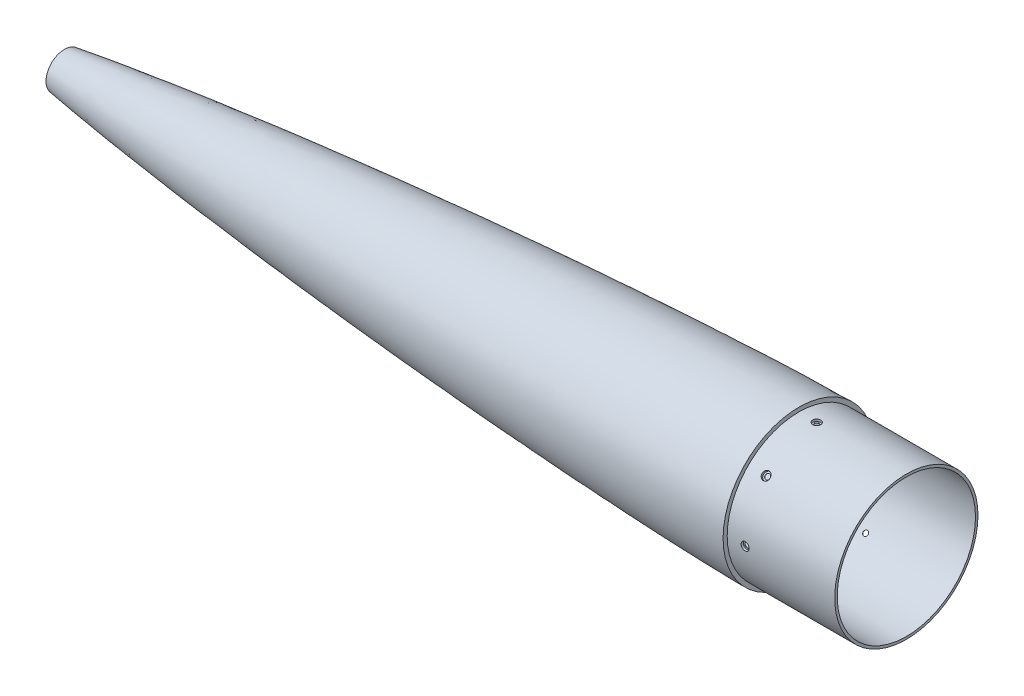
SolidWorks part; units mm, degrees
material "E-Glass Fiber"
ref_plane "Front Plane" through (0, 0, 0) normal (0, 0, 1) x (1, 0, 0)
ref_plane "Top Plane" through (0, 0, 0) normal (0, 1, 0) x (1, 0, 0)
ref_plane "Right Plane" through (0, 0, 0) normal (1, 0, 0) x (0, 0, -1)
sketch "Sketch2" plane through (0, 0, 0) normal (0, 0, 1) x (1, 0, 0)
  line L0 (0, 0) -> (584.2, 0)
  line L1 (584.2, 53.721) -> (584.2, 0)
  spline S0 degree 4 poles (0, 0) (0.0022, 0.0056) (0.0076, 0.0162) (0.0222, 0.0352) (0.0559, 0.0693) (0.1064, 0.1113) (0.1743, 0.1601) (0.2708, 0.2224) (0.3867, 0.2901) (0.5227, 0.3633) (0.6788, 0.4414) (0.9052, 0.5483) (1.2575, 0.7027) (1.8541, 0.9418) (2.9279, 1.3286) (4.8572, 1.9447) (8.3876, 2.9315) (14.9994, 4.5314) (26.6552, 6.951) (46.2509, 10.4452) (73.0277, 14.552) (105.3866, 18.9288) (141.1369, 23.265) (176.9301, 27.2281) (212.7562, 30.881) (248.6088, 34.2635) (284.4837, 37.3993) (320.3781, 40.3033) (356.29, 42.9823) (392.2179, 45.437) (428.1608, 47.6612) (464.1181, 49.6413) (495.5929, 51.1375) (522.5799, 52.2225) (544.3402, 52.9414) (558.9873, 53.3346) (571.0188, 53.5813) (578.5507, 53.684) (582.3169, 53.7167) (584.2, 53.721) knots 0 0 0 0 0 0.000041 0.000081 0.000163 0.000325 0.000488 0.00065 0.000944 0.001239 0.001539 0.001838 0.002649 0.003857 0.005913 0.009607 0.016434 0.028809 0.052217 0.090639 0.151931 0.213222 0.274513 0.335805 0.397096 0.458387 0.519679 0.58097 0.642262 0.703553 0.764844 0.826136 0.887427 0.918073 0.948719 0.974359 0.98718 1 1 1 1 1 construction
  spline S1 degree 4 poles (0, 0) (0.0022, 0.0056) (0.0076, 0.0162) (0.0222, 0.0352) (0.0559, 0.0693) (0.1064, 0.1113) (0.1743, 0.1601) (0.2708, 0.2224) (0.3867, 0.2901) (0.5227, 0.3633) (0.6788, 0.4414) (0.9052, 0.5483) (1.2575, 0.7027) (1.8541, 0.9418) (2.9279, 1.3286) (4.8572, 1.9447) (8.3876, 2.9315) (14.9994, 4.5314) (26.6552, 6.951) (46.2509, 10.4452) (73.0277, 14.552) (105.3866, 18.9288) (141.1369, 23.265) (176.9301, 27.2281) (212.7562, 30.881) (248.6088, 34.2635) (284.4837, 37.3993) (320.3781, 40.3033) (356.29, 42.9823) (392.2179, 45.437) (428.1608, 47.6612) (464.1181, 49.6413) (495.5929, 51.1375) (522.5799, 52.2225) (544.3402, 52.9414) (558.9873, 53.3346) (571.0188, 53.5813) (578.5507, 53.684) (582.3169, 53.7167) (584.2, 53.721) knots 0 0 0 0 0 0.000041 0.000081 0.000163 0.000325 0.000488 0.00065 0.000944 0.001239 0.001539 0.001838 0.002649 0.003857 0.005913 0.009607 0.016434 0.028809 0.052217 0.090639 0.151931 0.213222 0.274513 0.335805 0.397096 0.458387 0.519679 0.58097 0.642262 0.703553 0.764844 0.826136 0.887427 0.918073 0.948719 0.974359 0.98718 1 1 1 1 1
  dimension "D1" = 584.2
revolve "Nosecone Revolve" add sketch "Sketch2" angle 360 about L0
shell "Nosecone Shell" thickness 2.921 removed face at (584.2, 0, 53.721)
sketch "Shoulder Sketch" plane through (584.2, 0, 0) normal (1, 0, 0) x (0, 0, -1)
  circle A1 centre (0, 0) radius 50.8
  circle A2 centre (0, 0) radius 49.022
  dimension "D1" = 1.778
  dimension "D2" = 101.6
extrude "Shoulder" add sketch "Shoulder Sketch" along normal blind 76.2 and the other way blind 76.2 separate body
combine bodies "Combine1" operation type add bodies to combine 101 102
ref_plane "Tip cutting plane" through (63.5, 0, 0) normal (1, 0, 0) x (0, 0, -1)
sketch "Sketch4" plane through (63.5, 0, 0) normal (1, 0, 0) x (0, 0, -1)
  circle A0 centre (0, 0) radius 57.15
  dimension "D1" = 114.3
extrude "Tip Cut" cut sketch "Sketch4" against normal up to vertex (63.5 mm away) up to point (0, 0, 0)
ref_plane "Hole Plane" through (0, 0, -50.8) normal (0, 0, -1) x (-1, 0, 0)
sketch "Sketch5" plane through (0, 0, -50.8) normal (0, 0, -1) x (-1, 0, 0)
  line L0 (-584.2, 0) -> (-660.4, 0) construction
  line L1 (-584.2, 50.8) -> (-584.2, -50.8) construction
  line L2 (-660.4, 50.8) -> (-660.4, -50.8) construction
  circle A0 centre (-596.9, 0) radius 1.7526
  dimension "D1" = 3.5052
  dimension "D2" = 12.7
extrude "Bulkhead Screws" cut sketch "Sketch5" against normal up to next
pattern_circular "Screw Hole Pattern" count 8 over 360 about axis through (508, 0, 0) along (1, 0, 0) of "Bulkhead Screws" reverse direction yes
sketch "Sketch7" plane through (0, 0, -50.8) normal (0, 0, -1) x (-1, 0, 0)
  circle A0 centre (-596.9, 0) radius 1.7526 construction
  circle A1 centre (-596.9, 0) radius 1.7526
  circle A2 centre (-596.9, 0) radius 2.8702
  dimension "D1" = 5.7404
extrude "Hole CounterSink" cut sketch "Sketch7" against normal blind 1.5875
pattern_circular "CirPattern1" count 8 over 360 about axis through (508, 0, 0) along (1, 0, 0) of "Hole CounterSink"
